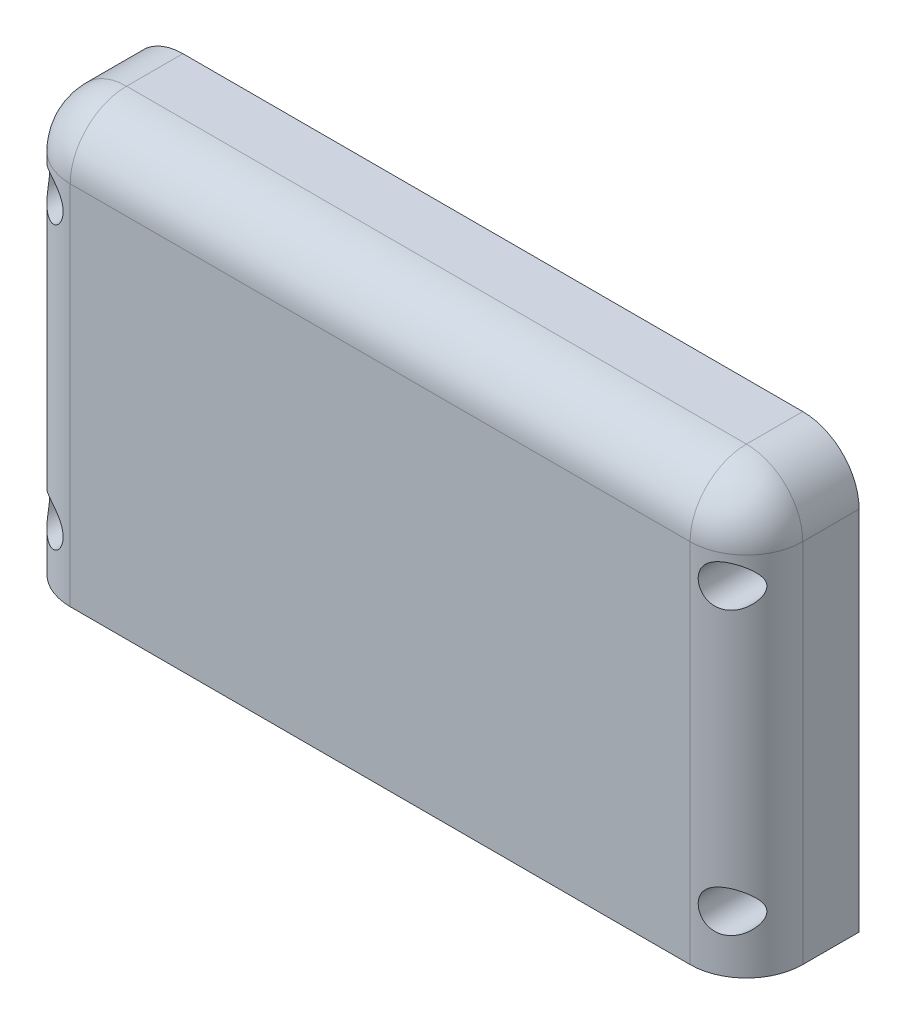
SolidWorks part; units mm, degrees
ref_plane "Front Plane" through (0, 0, 0) normal (0, 0, 1) x (1, 0, 0)
ref_plane "Top Plane" through (0, 0, 0) normal (0, 1, 0) x (1, 0, 0)
ref_plane "Right Plane" through (0, 0, 0) normal (1, 0, 0) x (0, 0, -1)
sketch "Sketch3" plane through (0, 0, 0) normal (0, 0, 1) x (1, 0, 0)
  line L1 (0, 0) -> (33.02, 0)
  line L2 (0, 0) -> (0, 19.05)
  line L3 (0, 19.05) -> (33.02, 19.05)
  line L4 (33.02, 0) -> (33.02, 19.05)
  dimension "D1" = 33.02
  dimension "D2" = 19.05
extrude "Boss-Extrude1" add sketch "Sketch3" along normal blind 5.08
hole_wizard "#49 (0.073) Diameter Hole1" positions "3DSketch1" profile "Sketch4" hole size "#49" standard "ANSI Inch" end condition through all
sketch3d "3DSketch1"
  line L0 (0, 19.05, 5.08) -> (0, 0, 5.08) construction
  line L1 (0, 0, 5.08) -> (33.02, 0, 5.08) construction
  line L2 (33.02, 0, 5.08) -> (33.02, 19.05, 5.08) construction
  point P0 (1.27, 15.24, 5.08)
  point P2 (1.27, 2.54, 5.08)
  point P4 (31.75, 15.24, 5.08)
  point P6 (31.75, 2.54, 5.08)
  dimension "D1" = 1.27
  dimension "D2" = 1.27
  dimension "D3" = 2.54
  dimension "D4" = 12.7
  dimension "D5" = 2.54
  dimension "D6" = 1.27
  dimension "D7" = 1.27
  dimension "D8" = 12.7
sketch "Sketch4" plane through (1.27, 15.24, 5.08) normal (1, 0, 0) x (0, -1, 0)
  line L0 (0, 0) -> (0, 5.08)
  line L1 (0, 5.08) -> (0.9271, 5.08)
  line L2 (0.9271, 5.08) -> (0.9271, 0)
  line L5 (0.9271, 0) -> (0, 0)
  line L11 (0, -6.35) -> (0, 107.95) construction
  dimension "Thru Hole Dia." = 1.8542
  dimension "Thru Hole Depth" = 5.08
fillet "Fillet1" radius 2.54 5 edges at (33.02, 9.525, 5.08) (16.51, 19.05, 5.08) (0, 9.525, 5.08) (33.02, 19.05, 2.54) (0, 19.05, 2.54)
